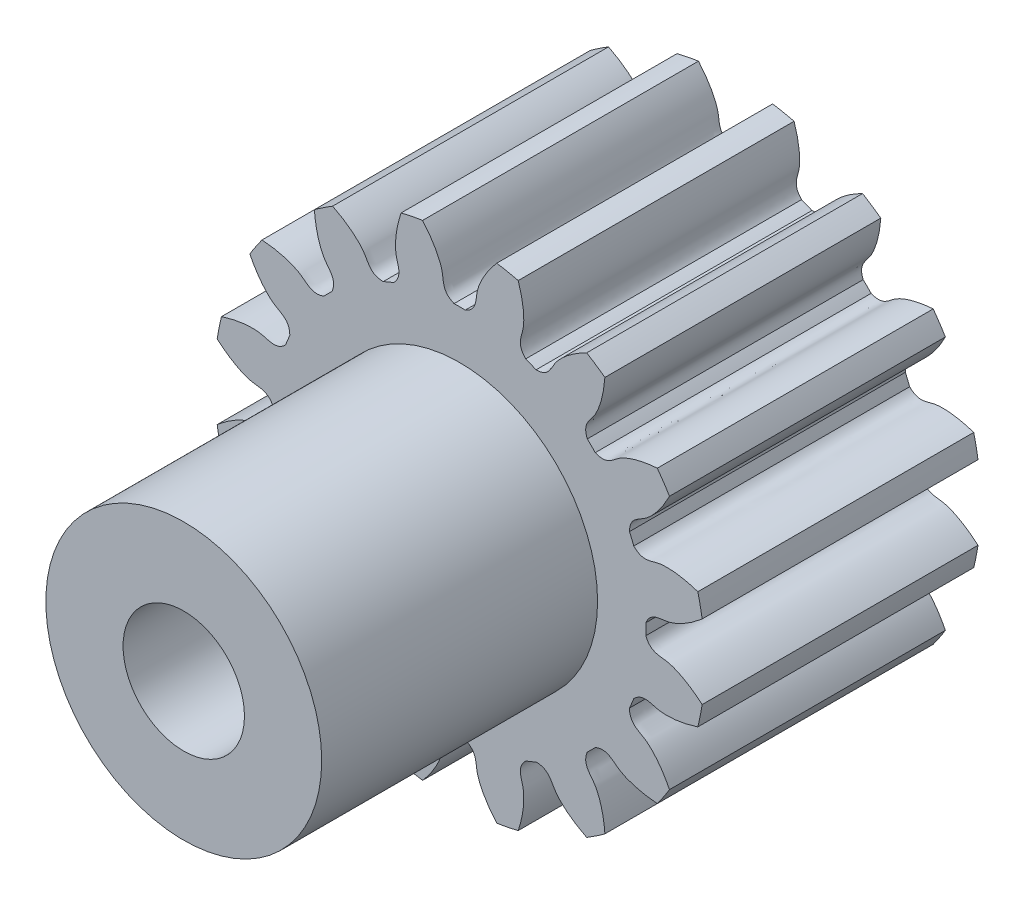
SolidWorks part; units mm, degrees
ref_plane "前视基准面" through (0, 0, 0) normal (0, 0, 1) x (1, 0, 0)
ref_plane "上视基准面" through (0, 0, 0) normal (0, 1, 0) x (1, 0, 0)
ref_plane "右视基准面" through (0, 0, 0) normal (1, 0, 0) x (0, 0, -1)
sketch "草图1" plane through (0, 0, 0) normal (0, 0, 1) x (1, 0, 0)
  circle A0 centre (0, 0) radius 4.4455
extrude "凸台-拉伸1" add sketch "草图1" along normal blind 5
ref_axis "基准轴1" through (0, 0, 5) along (0, 0, -1)
sketch "草图2" plane through (0, 0, 0) normal (0, 0, 1) x (1, 0, 0)
  line L0 (0, 0) -> (0, 4.4455) construction
  circle A0 centre (0, 0) radius 4.4455 construction
  arc A1 (0.1017, 3.3735) -> (-0.1017, 3.3735) centre (0, 0) ccw
  arc A2 (1.4955, 5.0459) -> (-1.4955, 5.0459) centre (0, 0) ccw
  spline S0 degree 3 poles (0.1017, 3.3735) (0.3209, 3.4651) (0.2847, 3.6353) (0.3224, 3.7934) (0.3256, 3.8058) (0.3295, 3.8195) (0.334, 3.8346) (0.3394, 3.8511) (0.3455, 3.8688) (0.3526, 3.8879) (0.3605, 3.9082) (0.3695, 3.9297) (0.3794, 3.9524) (0.3905, 3.9763) (0.4027, 4.0013) (0.4161, 4.0274) (0.4307, 4.0545) (0.4466, 4.0827) (0.4638, 4.1118) (0.4823, 4.1419) (0.5023, 4.1728) (0.5238, 4.2046) (0.5467, 4.2372) (0.5712, 4.2705) (0.5973, 4.3045) (0.6249, 4.3392) (0.6543, 4.3744) (0.6853, 4.4102) (0.718, 4.4465) (0.7524, 4.4833) (0.7887, 4.5204) (0.8267, 4.5578) (0.8666, 4.5955) (0.9084, 4.6334) (0.952, 4.6715) (0.9975, 4.7096) (1.045, 4.7478) (1.0944, 4.7859) (1.1457, 4.8239) (1.1991, 4.8618) (1.2544, 4.8994) (1.3117, 4.9367) (1.3917, 4.9866) (1.4534, 5.0225) (1.4955, 5.0459) knots 0 0 0 0 0.20766 0.212713 0.21844 0.224841 0.231916 0.239664 0.248086 0.257182 0.266951 0.277394 0.288511 0.300302 0.312767 0.325905 0.339717 0.354203 0.369362 0.385196 0.401703 0.418883 0.436738 0.455266 0.474469 0.494344 0.514894 0.536117 0.558015 0.580585 0.60383 0.627749 0.652341 0.677607 0.703546 0.73016 0.757447 0.785408 0.814043 0.843351 0.873333 0.903989 0.935319 1 1 1 1
  spline S1 degree 3 poles (-0.1017, 3.3735) (-0.3209, 3.4651) (-0.2847, 3.6353) (-0.3224, 3.7934) (-0.3256, 3.8058) (-0.3295, 3.8195) (-0.334, 3.8346) (-0.3394, 3.8511) (-0.3455, 3.8688) (-0.3526, 3.8879) (-0.3605, 3.9082) (-0.3695, 3.9297) (-0.3794, 3.9524) (-0.3905, 3.9763) (-0.4027, 4.0013) (-0.4161, 4.0274) (-0.4307, 4.0545) (-0.4466, 4.0827) (-0.4638, 4.1118) (-0.4823, 4.1419) (-0.5023, 4.1728) (-0.5238, 4.2046) (-0.5467, 4.2372) (-0.5712, 4.2705) (-0.5973, 4.3045) (-0.6249, 4.3392) (-0.6543, 4.3744) (-0.6853, 4.4102) (-0.718, 4.4465) (-0.7524, 4.4833) (-0.7887, 4.5204) (-0.8267, 4.5578) (-0.8666, 4.5955) (-0.9084, 4.6334) (-0.952, 4.6715) (-0.9975, 4.7096) (-1.045, 4.7478) (-1.0944, 4.7859) (-1.1457, 4.8239) (-1.1991, 4.8618) (-1.2544, 4.8994) (-1.3117, 4.9367) (-1.3917, 4.9866) (-1.4534, 5.0225) (-1.4955, 5.0459) knots 0 0 0 0 0.20766 0.212713 0.21844 0.224841 0.231916 0.239664 0.248086 0.257182 0.266951 0.277394 0.288511 0.300302 0.312767 0.325905 0.339717 0.354203 0.369362 0.385196 0.401703 0.418883 0.436738 0.455266 0.474469 0.494344 0.514894 0.536117 0.558015 0.580585 0.60383 0.627749 0.652341 0.677607 0.703546 0.73016 0.757447 0.785408 0.814043 0.843351 0.873333 0.903989 0.935319 1 1 1 1
extrude "切除-拉伸1" cut sketch "草图2" along normal through all
pattern_circular "阵列(圆周)1" count 16 over 360 about axis through (0, 0, 5) along (0, 0, -1) of "切除-拉伸1"
sketch "草图3" plane through (0, 0, 0) normal (0, 0, 1) x (1, 0, 0)
  circle A0 centre (0, 0) radius 4 construction
  dimension "Dn" = 8
sketch "草图4" plane through (0, 0, 5) normal (0, 0, 1) x (1, 0, 0)
  circle A0 centre (0, 0) radius 2.5
  dimension "D1" = 5
extrude "凸台-拉伸2" add sketch "草图4" along normal blind 5
sketch "草图5" plane through (0, 0, 10) normal (0, 0, 1) x (1, 0, 0)
  circle A0 centre (0, 0) radius 1.1
  dimension "D1" = 2.2
extrude "切除-拉伸2" cut sketch "草图5" against normal blind 5
